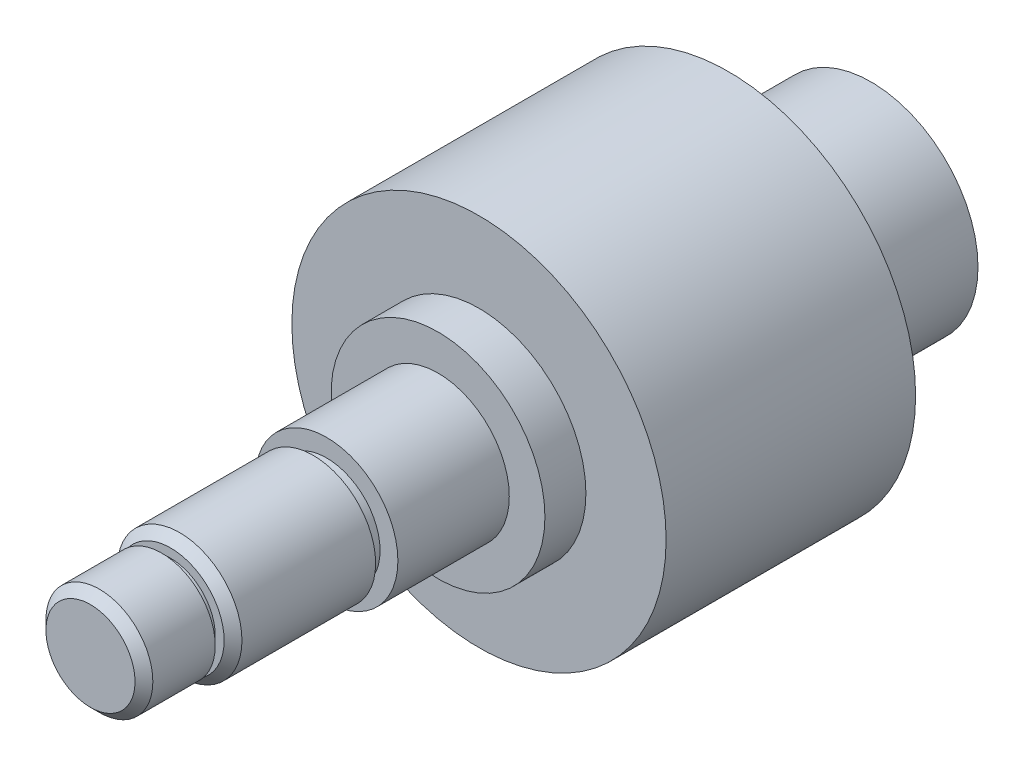
SolidWorks part; units mm, degrees
ref_plane "Plan de face" through (0, 0, 0) normal (0, 0, 1) x (1, 0, 0)
ref_plane "Plan de dessus" through (0, 0, 0) normal (0, 1, 0) x (1, 0, 0)
ref_plane "Plan de droite" through (0, 0, 0) normal (1, 0, 0) x (0, 0, -1)
sketch "Esquisse1" plane through (0, 0, 0) normal (0, 0, 1) x (1, 0, 0)
  circle A0 centre (0, 0) radius 6
  dimension "D1" = 12
extrude "Boss.-Extru.1" add sketch "Esquisse1" along normal blind 8
sketch "Esquisse2" plane through (0, 0, 8) normal (0, 0, 1) x (1, 0, 0)
  circle A0 centre (0, 0) radius 10.5
  dimension "D1" = 21
extrude "Boss.-Extru.2" add sketch "Esquisse2" along normal blind 14
sketch "Esquisse3" plane through (0, 0, 22) normal (0, 0, 1) x (1, 0, 0)
  circle A0 centre (0, 0) radius 6
  dimension "D1" = 12
extrude "Boss.-Extru.3" add sketch "Esquisse3" along normal blind 2.3
sketch "Esquisse4" plane through (0, 0, 24.3) normal (0, 0, 1) x (1, 0, 0)
  circle A0 centre (0, 0) radius 4
  dimension "D1" = 8
extrude "Boss.-Extru.4" add sketch "Esquisse4" along normal blind 6.25
sketch "Esquisse5" plane through (0, 0, 30.55) normal (0, 0, 1) x (1, 0, 0)
  circle A0 centre (0, 0) radius 3
  dimension "D1" = 6
extrude "Boss.-Extru.5" add sketch "Esquisse5" along normal blind 0.75
sketch "Esquisse7" plane through (0, 0, 31.3) normal (0, 0, 1) x (1, 0, 0)
  circle A0 centre (0, 0) radius 3.5
  dimension "D1" = 7
extrude "Boss.-Extru.6" add sketch "Esquisse7" along normal blind 8
sketch "Esquisse8" plane through (0, 0, 39.3) normal (0, 0, 1) x (1, 0, 0)
  circle A0 centre (0, 0) radius 2.5
  dimension "D1" = 5
extrude "Boss.-Extru.7" add sketch "Esquisse8" along normal blind 0.5
sketch "Esquisse9" plane through (0, 0, 39.8) normal (0, 0, 1) x (1, 0, 0)
  circle A0 centre (0, 0) radius 3
  dimension "D1" = 6
extrude "Boss.-Extru.8" add sketch "Esquisse9" along normal blind 4
sketch "Esquisse10" plane through (0, 0, 0) normal (0, 0, -1) x (-1, 0, 0)
  circle A0 centre (0, 0) radius 4.75
  dimension "D1" = 9.5
extrude "Enlèv. mat.-Extru.1" cut sketch "Esquisse10" against normal blind 21
chamfer "Chanfrein1" distance 0.5 angle 45 1 edges at (3.5, 0, 39.3)
chamfer "Chanfrein2" distance 0.5 angle 45 1 edges at (3, 0, 43.8)
